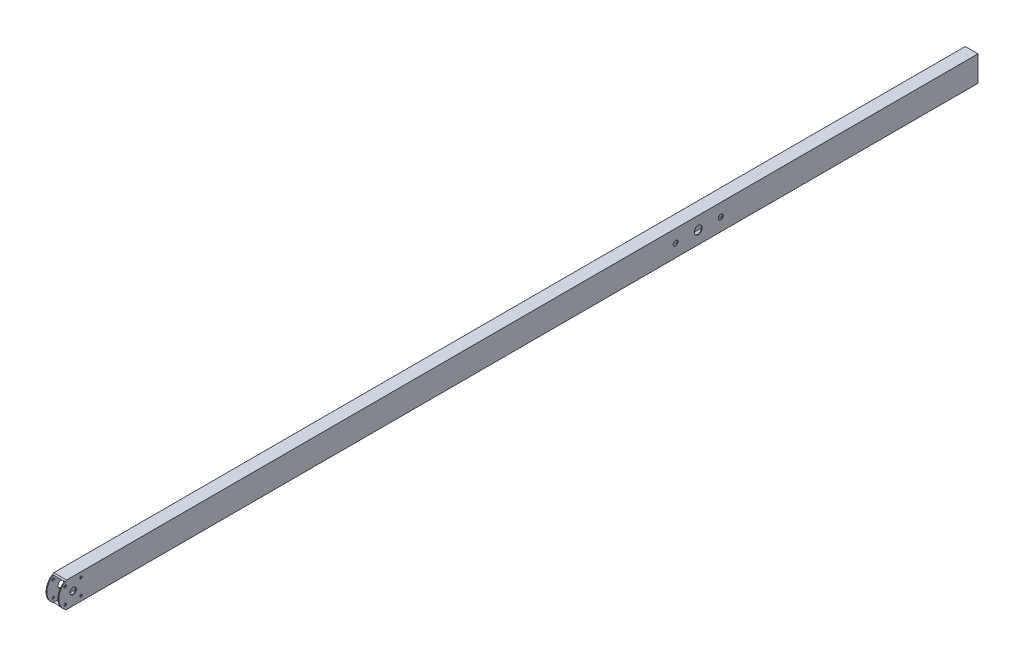
SolidWorks part; units mm, degrees
ref_plane "Front Plane" through (0, 0, 0) normal (0, 0, 1) x (1, 0, 0)
ref_plane "Top Plane" through (0, 0, 0) normal (0, 1, 0) x (1, 0, 0)
ref_plane "Right Plane" through (0, 0, 0) normal (1, 0, 0) x (0, 0, -1)
sketch "Sketch2" plane through (0, 0, 0) normal (0, 0, 1) x (1, 0, 0)
  line L1 (12.7, -25.4) -> (-12.7, -25.4)
  line L2 (12.7, -25.4) -> (12.7, 25.4)
  line L3 (12.7, 25.4) -> (-12.7, 25.4)
  line L4 (-12.7, -25.4) -> (-12.7, 25.4)
  line L5 (12.7, -25.4) -> (-12.7, 25.4) construction
  line L6 (12.7, 25.4) -> (-12.7, -25.4) construction
  point P1 (0, 0)
  dimension "D1" = 25.4
  dimension "D2" = 50.8
extrude "Extrude-Thin2" add sketch "Sketch2" along normal blind 1828.8 thin thin type one direction reverse wall 1.5875
sketch "Sketch8" plane through (12.7, 0, 0) normal (1, 0, 0) x (0, 0, -1)
  line L3 (-1800.225, -28.575) -> (-1800.225, 28.575)
  line L7 (0, -25.4) -> (0, 25.4)
  line L8 (0, 25.4) -> (-1828.8, 25.4)
  line L9 (-1828.8, 25.4) -> (-1828.8, -25.4)
  line L10 (-1828.8, -25.4) -> (0, -25.4)
  line L11 (0, -25.4) -> (0, 25.4)
  line L12 (0, 25.4) -> (-1828.8, 25.4)
  line L13 (-1828.8, 25.4) -> (-1828.8, -25.4)
  line L14 (-1828.8, -25.4) -> (0, -25.4)
  arc A0 (-1800.225, 28.575) -> (-1800.225, -28.575) centre (-1800.225, 0) ccw
  point P4 (-1828.8, 0)
  point P5 (-1828.8, 0)
  line M13 (-1828.8, 25.4) -> (-1828.8, -25.4)
  line M14 (-1828.8, -25.4) -> (0, -25.4)
  dimension "D2" = 57.15
  dimension "D1" = 0
extrude "Cut-Extrude1" cut sketch "Sketch8" against normal through all contours A0 L12 M13 | A0 L13 M14 region at (12.7, -19.4433, 1824.4944) region at (12.7, 19.4433, 1824.4944)
hole_wizard "1/2 (0.5) Diameter Hole2" positions "Sketch9" profile "Sketch10" hole size "1/2" standard "ANSI Inch" end condition through all
sketch "Sketch9" plane through (12.7, 0, 0) normal (1, 0, 0) x (0, 0, -1)
  point P0 (-1800.225, 0)
sketch "Sketch10" plane through (12.7, 0, 1800.225) normal (0, 1, 0) x (0, 0, -1)
  line L0 (0, 0) -> (0, 25.4)
  line L1 (0, 25.4) -> (6.35, 25.4)
  line L2 (6.35, 25.4) -> (6.35, 0)
  line L5 (6.35, 0) -> (0, 0)
  line L11 (0, -6.35) -> (0, 107.95) construction
  dimension "Thru Hole Dia." = 12.7
  dimension "Thru Hole Depth" = 25.4
sketch "Sketch3" plane through (12.7, 0, 0) normal (1, 0, 0) x (0, 0, -1)
  line L0 (-601.6355, 0) -> (-511.5449, 0)
  line L8 (-1813.3159, 25.4) -> (0, 25.4) construction
  line L9 (-1813.3159, -25.4) -> (0, -25.4) construction
  line L10 (-556.5902, 25.4) -> (-556.5902, -25.4) construction
  circle A0 centre (-1800.225, 0) radius 6.35 construction
  point P0 (-556.5902, 0)
  point P8 (-556.5902, 0)
  point P18 (-556.5902, 0)
  dimension "D2" = 90.0906
  dimension "D1" = 1243.6348
hole_wizard "5/8 (0.625) Diameter Hole1" positions "Sketch4" profile "Sketch5" hole size "5/8" standard "ANSI Inch" end condition through all
sketch "Sketch4" plane through (12.7, 0, 0) normal (1, 0, 0) x (0, 0, -1)
  point P0 (-556.5902, 0)
sketch "Sketch5" plane through (12.7, 0, 556.5902) normal (0, 1, 0) x (0, 0, -1)
  line L0 (0, 0) -> (0, 25.4)
  line L1 (0, 25.4) -> (7.9375, 25.4)
  line L2 (7.9375, 25.4) -> (7.9375, 0)
  line L5 (7.9375, 0) -> (0, 0)
  line L11 (0, -6.35) -> (0, 107.95) construction
  dimension "Thru Hole Dia." = 15.875
  dimension "Thru Hole Depth" = 25.4
hole_wizard "3/8 (0.375) Diameter Hole1" positions "Sketch11" profile "Sketch12" hole size "3/8" standard "ANSI Inch" end condition through all
sketch "Sketch11" plane through (12.7, 0, 0) normal (1, 0, 0) x (0, 0, -1)
  point P0 (-601.6355, 0)
  point P3 (-511.5449, 0)
sketch "Sketch12" plane through (12.7, 0, 601.6355) normal (0, 1, 0) x (0, 0, -1)
  line L0 (0, 0) -> (0, 25.4)
  line L1 (0, 25.4) -> (4.7625, 25.4)
  line L2 (4.7625, 25.4) -> (4.7625, 0)
  line L5 (4.7625, 0) -> (0, 0)
  line L11 (0, -6.35) -> (0, 107.95) construction
  dimension "Thru Hole Dia." = 9.525
  dimension "Thru Hole Depth" = 25.4
sketch "Sketch13" plane through (12.7, 0, 0) normal (1, 0, 0) x (0, 0, -1)
  circle A0 centre (-1800.225, 0) radius 27.813 construction
  circle A1 centre (-1800.225, 0) radius 27.813
  circle A2 centre (-1815.9404, -15.7154) radius 2.2479 construction
  circle A3 centre (-1815.9404, 15.7154) radius 2.2479 construction
  circle A4 centre (-1784.5096, -15.7154) radius 2.2479 construction
  circle A5 centre (-1784.5096, 15.7154) radius 2.2479 construction
  circle A6 centre (-1815.9404, -15.7154) radius 2.2479
  circle A7 centre (-1815.9404, 15.7154) radius 2.2479
  circle A8 centre (-1784.5096, -15.7154) radius 2.2479
  circle A9 centre (-1784.5096, 15.7154) radius 2.2479
hole_wizard "3/16 (0.1875) Diameter Hole1" positions "Sketch14" profile "Sketch15" hole size "3/16" standard "ANSI Inch" end condition through all
sketch "Sketch14" plane through (12.7, 0, 0) normal (1, 0, 0) x (0, 0, -1)
  point P0 (-1784.5096, 15.7154)
  point P2 (-1784.5096, -15.7154)
  point P5 (-1815.9404, -15.7154)
  point P8 (-1815.9404, 15.7154)
  point P11 (0, 0)
sketch "Sketch15" plane through (12.7, 15.7154, 1784.5096) normal (0, 1, 0) x (0, 0, -1)
  line L0 (0, 0) -> (0, 25.4)
  line L1 (0, 25.4) -> (2.3812, 25.4)
  line L2 (2.3812, 25.4) -> (2.3812, 0)
  line L5 (2.3812, 0) -> (0, 0)
  line L11 (0, -6.35) -> (0, 107.95) construction
  dimension "Thru Hole Dia." = 4.7625
  dimension "Thru Hole Depth" = 25.4
equation "\"H\"=2"
equation "\"W\"= 1"
equation "\"Wall\"= 1 / 16"
equation "\"D1@Sketch2\"=\"W\""
equation "\"D2@Sketch2\"= \"H\""
equation "\"D5@Extrude-Thin2\"=\"Wall\""
equation "\"FHspacing\"= 3 + 35 / 64"
equation "\"L\"=72"
equation "\"D1@Extrude-Thin2\"=\"L\""
equation "\"D2@Sketch3\"=\"FHspacing\""
equation "\"Shaft2Shaft\"= 48.962"
equation "\"D1@Sketch3\"=\"Shaft2Shaft\""
